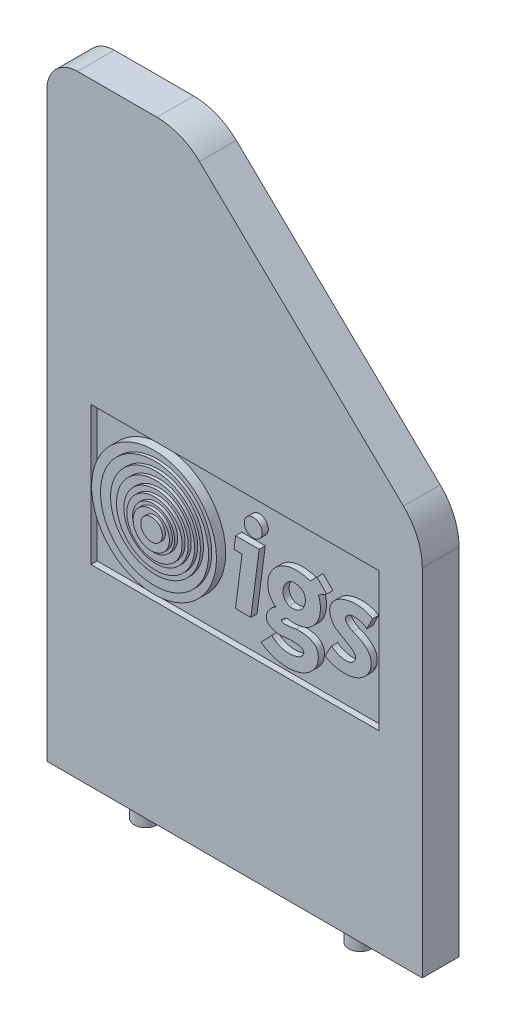
SolidWorks part; units mm, degrees
ref_plane "Front Plane" through (0, 0, 0) normal (0, 0, 1) x (1, 0, 0)
ref_plane "Top Plane" through (0, 0, 0) normal (0, 1, 0) x (1, 0, 0)
ref_plane "Right Plane" through (0, 0, 0) normal (1, 0, 0) x (0, 0, -1)
sketch "Sketch4" plane through (0, 0, 0) normal (0, 0, 1) x (1, 0, 0)
  line L1 (0, 0) -> (122.5, 0)
  line L2 (0, 0) -> (0, 200)
  line L3 (0, 200) -> (122.5, 200)
  line L4 (122.5, 0) -> (122.5, 200)
  dimension "D1" = 122.5
  dimension "D2" = 200
extrude "Boss-Extrude1" add sketch "Sketch4" along normal blind 12
sketch "Sketch7" plane through (0, 0, 12) normal (0, 0, 1) x (1, 0, 0)
  line L1 (122.5, 200) -> (0, 200) construction
  line L2 (43.9858, 200) -> (122.5, 124.4158)
  line L3 (122.5, 0) -> (122.5, 200) construction
  line L4 (43.9858, 200) -> (122.5, 200)
  line L5 (122.5, 200) -> (122.5, 124.4158)
extrude "Cut-Extrude1" cut sketch "Sketch7" against normal blind 12
fillet "Fillet1" radius 20 1 edges at (43.9858, 200, 6)
fillet "Fillet2" radius 20 1 edges at (122.5, 124.4158, 6)
fillet "Fillet3" radius 10 1 edges at (0, 200, 6)
sketch "Sketch10" plane through (0, 0, 0) normal (0, -1, 0) x (1, 0, 0)
  circle A0 centre (26.25, 6) radius 3.75
  circle A1 centre (96.25, 6) radius 3.75
extrude "Boss-Extrude3" add sketch "Sketch10" along normal blind 6
sketch "Sketch11" plane through (0, -6, 0) normal (0, -1, 0) x (1, 0, 0)
  circle A0 centre (26.25, 6) radius 3.75
  circle A1 centre (96.25, 6) radius 3.75
extrude "Boss-Extrude4" add sketch "Sketch11" along normal blind 2 draft 62
sketch "Sketch12" plane through (0, 0, 0) normal (-1, 0, 0) x (0, 0, 1)
  line L0 (12, 0) -> (12, 10)
  line L1 (0, 190) -> (0, 0) construction
  line L2 (0, 180) -> (12, 180)
  line L3 (12, 190) -> (12, 0) construction
  line L4 (6, 190) -> (6, 180)
  line L5 (12, 190) -> (0, 190) construction
  line L6 (12, 10) -> (6, 10)
  line L7 (6, 10) -> (6, 0)
  line L8 (12, 0) -> (0, 0) construction
hole_wizard "Ø5.0 (5) Diameter Hole1" positions "Sketch14" profile "Sketch13" hole size "Ø5.0" standard "ANSI Metric"
sketch "Sketch14" plane through (0, 0, 0) normal (-1, 0, 0) x (0, 0, 1)
  point P0 (6, 180)
sketch "Sketch13" plane through (0, 180, 6) normal (0, 1, 0) x (0, 0, 1)
  line L0 (0, 0) -> (0, 9.5022)
  line L1 (0, 9.5022) -> (2.5, 8)
  line L2 (2.5, 8) -> (2.5, 0)
  line L5 (2.5, 0) -> (0, 0)
  line L10 (0, 9.5022) -> (-2.5, 8) construction
  line L11 (0, -6.35) -> (0, 107.95) construction
  dimension "Hole Dia." = 5
  dimension "Hole Depth" = 8
  dimension "Drill Angle" = 118
hole_wizard "Ø5.0 (5) Diameter Hole2" positions "Sketch17" profile "Sketch16" hole size "Ø5.0" standard "ANSI Metric"
sketch "Sketch17" plane through (0, 0, 0) normal (-1, 0, 0) x (0, 0, 1)
  point P0 (6, 10)
sketch "Sketch16" plane through (0, 10, 6) normal (0, 1, 0) x (0, 0, 1)
  line L0 (0, 0) -> (0, 9.5022)
  line L1 (0, 9.5022) -> (2.5, 8)
  line L2 (2.5, 8) -> (2.5, 0)
  line L5 (2.5, 0) -> (0, 0)
  line L10 (0, 9.5022) -> (-2.5, 8) construction
  line L11 (0, -6.35) -> (0, 107.95) construction
  dimension "Hole Dia." = 5
  dimension "Hole Depth" = 8
  dimension "Drill Angle" = 118
sketch "Sketch20" plane through (0, 0, 12) normal (0, 0, 1) x (1, 0, 0)
  line L0 (61.589, 94.5578) -> (61.0476, 90.4302)
  line L1 (61.0476, 90.4302) -> (63.6836, 90.4302)
  line L2 (63.6836, 90.4302) -> (61.5223, 73.954)
  line L3 (61.5223, 73.954) -> (66.5575, 73.954)
  line L4 (66.5575, 73.954) -> (69.2603, 94.5578)
  line L5 (69.2603, 94.5578) -> (61.589, 94.5578)
  line L6 (85.9622, 93.9515) -> (88.1267, 96.1161)
  line L7 (88.1267, 96.1161) -> (91.3322, 92.9106)
  line L8 (91.3322, 92.9106) -> (88.5902, 91.3162)
  line L9 (73.3769, 72.3167) -> (69.8838, 68.5658)
  line L10 (92.895, 79.0291) -> (90.7509, 75.2264)
  line L11 (14.3932, 108.0646) -> (108.3289, 108.0646)
  line L12 (14.3932, 108.0646) -> (14.3932, 62.823)
  line L13 (14.3932, 62.823) -> (108.3289, 62.823)
  line L14 (108.3289, 108.0646) -> (108.3289, 62.823)
  line L15 (106.2836, 93.4051) -> (104.3797, 89.5984)
  circle A0 centre (35.9576, 86.0138) radius 20.3765
  circle A1 centre (37.1191, 86.8188) radius 17.6415
  circle A2 centre (38.4286, 88.108) radius 14.6637
  circle A3 centre (39.442, 88.4286) radius 12.7455
  circle A4 centre (40.5933, 89.1353) radius 10.5049
  circle A5 centre (41.0999, 89.2956) radius 9.0198
  circle A6 centre (41.7954, 90.3335) radius 6.8376
  circle A7 centre (42.055, 90.4302) radius 5.9112
  circle A8 centre (43.1343, 91.6078) radius 3.5257
  circle A9 centre (67.3223, 99.6975) radius 2.9249
  spline S0 degree 3 poles (85.9622, 93.9515) (73.2279, 98.0393) (68.5654, 84.7099) (74.8171, 80.9748) knots 0 0 0 0 1 1 1 1
  spline S1 degree 3 poles (88.5902, 91.3162) (90.6088, 86.5647) (88.1952, 78.0326) (78.5038, 79.5633) knots 0 0 0 0 1 1 1 1
  spline S2 degree 3 poles (82.5068, 90.4302) (78.1391, 92.7685) (74.6774, 85.2467) (79.0624, 83.437) knots 0 0 0 0 1 1 1 1
  spline S3 degree 3 poles (82.5068, 90.4302) (85.7733, 89.8441) (84.7184, 82.2299) (79.0624, 83.437) knots 0 0 0 0 1 1 1 1
  spline S4 degree 3 poles (74.8171, 80.9748) (72.9226, 80.4101) (68.0414, 74.5281) (75.937, 73.7264) knots 0 0 0 0 1 1 1 1
  spline S5 degree 3 poles (75.937, 73.7264) (86.1934, 75.2288) (84.1571, 71.6569) (82.351, 70.6858) knots 0 0 0 0 1 1 1 1
  spline S6 degree 3 poles (82.351, 70.6858) (79.0709, 69.3296) (75.4109, 70.0569) (73.3769, 72.3167) knots 0 0 0 0 1 1 1 1
  spline S7 degree 3 poles (69.8838, 68.5658) (75.4411, 64.3568) (85.0078, 64.5589) (88.1267, 71.179) knots 0 0 0 0 1 1 1 1
  spline S8 degree 2 poles (88.1267, 71.179) (90.3532, 78.3554) (81.2969, 78.0673) knots 0 0 0 1 1 1
  spline S9 degree 3 poles (78.5038, 79.5633) (75.1064, 78.0839) (76.1553, 76.8593) (81.2969, 78.0673) knots 0 0 0 0 1 1 1 1
  spline S10 degree 3 poles (106.2836, 93.4051) (100.031, 97.4189) (87.9837, 92.6786) (93.8542, 84.9692) knots 0 0 0 0 1 1 1 1
  spline S11 degree 3 poles (93.8542, 84.9692) (98.0267, 82.0967) (102.6402, 80.96) (99.9114, 78.0673) knots 0 0 0 0 1 1 1 1
  spline S12 degree 3 poles (99.9114, 78.0673) (98.9582, 76.8044) (95.3467, 76.9706) (92.895, 79.0291) knots 0 0 0 0 1 1 1 1
  spline S13 degree 3 poles (90.7509, 75.2264) (94.2914, 72.6537) (103.1012, 72.0663) (105.5826, 78.7744) knots 0 0 0 0 1 1 1 1
  spline S14 degree 3 poles (105.5826, 78.7744) (106.4591, 82.6515) (104.5919, 84.8421) (99.9114, 86.5814) knots 0 0 0 0 1 1 1 1
  spline S15 degree 3 poles (99.9114, 86.5814) (94.7551, 89.0867) (99.081, 91.2635) (100.1462, 90.9918) knots 0 0 0 0 1 1 1 1
  spline S16 degree 2 poles (100.1462, 90.9918) (102.8609, 91.0098) (104.3797, 89.5984) knots 0 0 0 1 1 1
extrude "Cut-Extrude2" cut sketch "Sketch20" against normal blind 2 contours L14 L11 L12 L13 S16 S15 S14 S13 L10 S12 S11 S10 L15 A9 A0 L5 L4 L3 L2 L1 L0 S1 S9 S8 S7 L9 S6 S5 S4 S0 L6 L7 L8 region at (69.6587, 85.7582, 12)
extrude "Boss-Extrude13" add sketch "Sketch20<13>" along normal blind 1 contours A0 A1 region at (16.1574, 86.0138, 12)
sketch "Sketch20<13>" plane through (0, 0, 12) normal (0, 0, 1) x (1, 0, 0) same geometry as "Sketch20"
extrude "Boss-Extrude14" add sketch "Sketch20<14>" along normal blind 2 contours A1 A2 region at (19.9765, 86.8188, 12)
sketch "Sketch20<14>" plane through (0, 0, 12) normal (0, 0, 1) x (1, 0, 0) same geometry as "Sketch20"
extrude "Boss-Extrude15" add sketch "Sketch20<15>" along normal blind 3 contours A2 A3 region at (24.1797, 88.108, 12)
sketch "Sketch20<15>" plane through (0, 0, 12) normal (0, 0, 1) x (1, 0, 0) same geometry as "Sketch20"
extrude "Boss-Extrude16" add sketch "Sketch20<16>" along normal blind 4 contours A3 A4 region at (27.057, 88.4286, 12)
sketch "Sketch20<16>" plane through (0, 0, 12) normal (0, 0, 1) x (1, 0, 0) same geometry as "Sketch20"
extrude "Boss-Extrude17" add sketch "Sketch20<17>" along normal blind 5 contours A4 A5 region at (30.3854, 89.1353, 12)
sketch "Sketch20<17>" plane through (0, 0, 12) normal (0, 0, 1) x (1, 0, 0) same geometry as "Sketch20"
extrude "Boss-Extrude18" add sketch "Sketch20<18>" along normal blind 6 contours A5 A6 region at (32.3352, 89.2956, 12)
sketch "Sketch20<18>" plane through (0, 0, 12) normal (0, 0, 1) x (1, 0, 0) same geometry as "Sketch20"
extrude "Boss-Extrude19" add sketch "Sketch20<19>" along normal blind 7 contours A6 A7 region at (35.1512, 90.3335, 12)
sketch "Sketch20<19>" plane through (0, 0, 12) normal (0, 0, 1) x (1, 0, 0) same geometry as "Sketch20"
extrude "Boss-Extrude20" add sketch "Sketch20<20>" along normal blind 8 contours A7 A8 region at (36.311, 90.4302, 12)
sketch "Sketch20<20>" plane through (0, 0, 12) normal (0, 0, 1) x (1, 0, 0) same geometry as "Sketch20"
extrude "Boss-Extrude21" add sketch "Sketch20<21>" along normal blind 9 contours A8 region at (43.1343, 91.6078, 12)
sketch "Sketch20<21>" plane through (0, 0, 12) normal (0, 0, 1) x (1, 0, 0) same geometry as "Sketch20"
extrude "Cut-Extrude3" cut sketch "Sketch20<22>" against normal blind 2 contours S3 S2 region at (80.6864, 87.0701, 12)
sketch "Sketch20<22>" plane through (0, 0, 12) normal (0, 0, 1) x (1, 0, 0) same geometry as "Sketch20"
